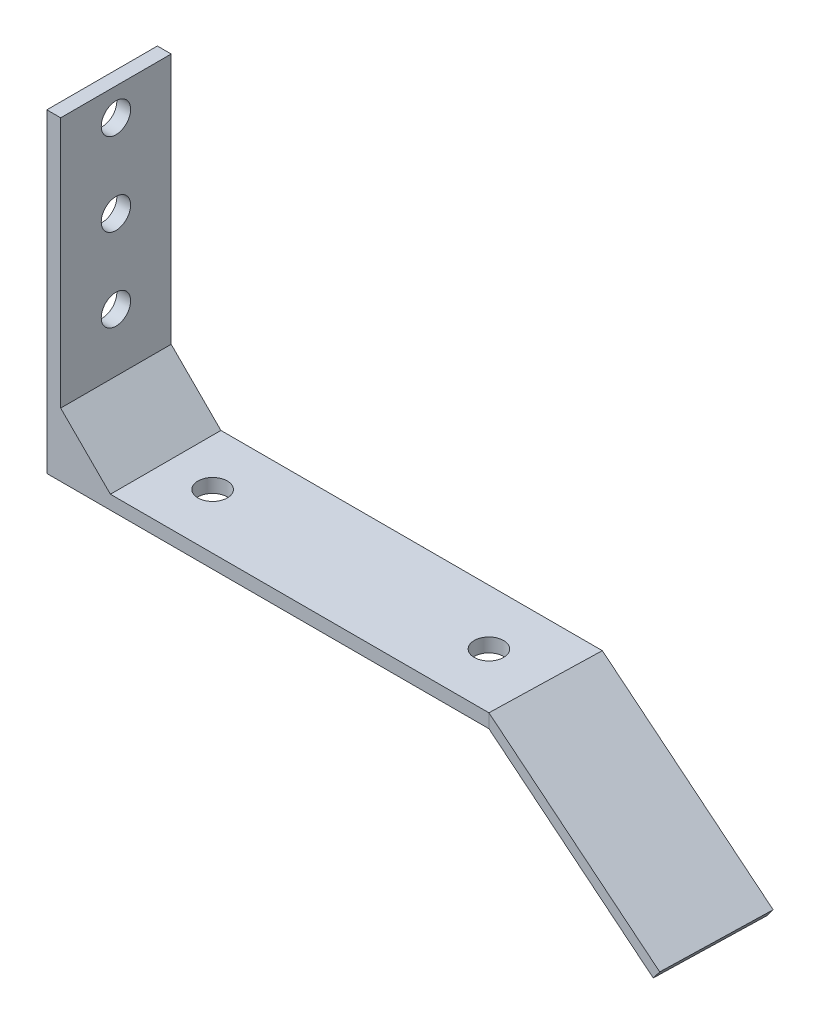
SolidWorks part; units mm, degrees
ref_plane "Front Plane" through (0, 0, 0) normal (0, 0, 1) x (1, 0, 0)
ref_plane "Top Plane" through (0, 0, 0) normal (0, 1, 0) x (1, 0, 0)
ref_plane "Right Plane" through (0, 0, 0) normal (1, 0, 0) x (0, 0, -1)
sketch "Sketch1" plane through (0, 0, 0) normal (0, 0, 1) x (1, 0, 0)
  line L1 (0, 0) -> (3.175, 0)
  line L2 (0, 0) -> (0, 72.39)
  line L3 (0, 72.39) -> (3.175, 72.39)
  line L4 (3.175, 3.175) -> (3.175, 72.39)
  line L5 (0, 0) -> (101.6, 0)
  line L6 (0, 0) -> (0, 3.175)
  line L7 (3.175, 3.175) -> (101.6, 3.175)
  line L8 (101.6, 0) -> (101.6, 3.175)
  dimension "D1" = 101.6
  dimension "D2" = 3.175
  dimension "D3" = 3.175
  dimension "D4" = 72.39
extrude "Boss-Extrude1" add sketch "Sketch1" along normal blind 25.4 contours L5 L8 L7 L4 L3 L2 L1 region at (1.2475, 1.5875, 0)
sketch "Sketch2" plane through (0, 3.175, 0) normal (0, 1, 0) x (1, 0, 0)
  line L0 (101.6, -25.4) -> (101.6, 0) construction
  line L1 (3.175, -25.4) -> (101.6, -25.4) construction
  circle A0 centre (88.9, -12.7) radius 3.3782
  circle A1 centre (25.4, -12.7) radius 3.3782
  dimension "D5" = 6.7564
  dimension "D6" = 6.7564
  dimension "D2" = 63.5
  dimension "D1" = 12.7
  dimension "D3" = 12.7
  dimension "D4" = 12.7
extrude "Cut-Extrude1" cut sketch "Sketch2" against normal blind 25.4
sketch "Sketch3" plane through (0, 0, 0) normal (-1, 0, 0) x (0, 0, 1)
  line L0 (25.4, 0) -> (0, 0) construction
  line L2 (0, 3.175) -> (0, 72.39) construction
  circle A0 centre (12.7, 27.94) radius 3.3782
  circle A1 centre (12.7, 46.99) radius 3.3782
  circle A2 centre (12.7, 66.04) radius 3.3782
  dimension "D1" = 6.7564
  dimension "D2" = 6.7564
  dimension "D3" = 6.7564
  dimension "D4" = 27.94
  dimension "D5" = 19.05
  dimension "D6" = 19.05
  dimension "D7" = 12.7
  dimension "D8" = 12.7
  dimension "D9" = 12.7
extrude "Cut-Extrude2" cut sketch "Sketch3" against normal through all
sketch "Sketch4" plane through (0, 0, 25.4) normal (0, 0, 1) x (1, 0, 0)
  line L0 (3.175, 14.605) -> (14.605, 3.175)
  line L1 (3.175, 3.175) -> (3.175, 72.39) construction
  line L2 (3.175, 3.175) -> (101.6, 3.175) construction
  line L3 (14.605, 3.175) -> (3.175, 3.175)
  line L4 (3.175, 3.175) -> (3.175, 14.605)
  dimension "D1" = 45
  dimension "D2" = 11.43
extrude "Boss-Extrude2" add sketch "Sketch4" against normal blind 25.4
sketch "Sketch5" plane through (0, 3.175, 0) normal (0, 1, 0) x (1, 0, 0)
  line L0 (101.6, -25.4) -> (102.2651, 0)
  line L1 (102.2651, 0) -> (101.6, 0)
  line L2 (101.6, 0) -> (96.08, -4.1638)
  line L3 (96.08, -4.1638) -> (98.1305, -10.2156)
  line L4 (98.1305, -10.2156) -> (94.0294, -12.2161)
  line L5 (94.0294, -12.2161) -> (96.08, -18.2679)
  line L6 (96.08, -18.2679) -> (92.6626, -19.9349)
  line L7 (92.6626, -19.9349) -> (98.1305, -22.4716)
  line L8 (98.1305, -22.4716) -> (98.84, -24.5653)
  line L9 (98.84, -24.5653) -> (101.6, -25.4)
  dimension "D1" = 88.5
extrude "Boss-Extrude3" add sketch "Sketch5" against normal up to surface (3.175 mm away) up to face at (25.4, 0, 16.0782)
ref_plane "Plane1" through (39.3186, 51.3512, 1.0296) normal (0.6079, 0.7939, 0.0159) x (0.0262, 0, -0.9997)
sketch "Sketch6" plane through (39.3186, 51.3512, 1.0296) normal (0.6079, 0.7939, 0.0159) x (0.0262, 0, -0.9997)
  line L0 (-22.7317, -79.2282) -> (-22.7317, -130.0282)
  line L2 (-22.7317, -130.0282) -> (2.677, -130.0282)
  line L3 (2.677, -79.2282) -> (2.677, -130.0282)
  line L7 (-22.7317, -79.2282) -> (2.677, -79.2282)
  dimension "D1" = 50.8
extrude "Boss-Extrude4" add sketch "Sketch6" against normal up to vertex (2.5206 mm away) up to point (102.2651, 0, 0)
sketch "Sketch7" plane through (0, 0, 0) normal (-1, 0, 0) x (0, 0, 1)
  line L0 (0, 0) -> (0, 72.39) construction
  line L1 (0, 12.8186) -> (-4.5061, 12.8186)
  line L2 (0, 12.8186) -> (0, 0)
  line L3 (0, 0) -> (-4.5061, 0)
  line L4 (-4.5061, 12.8186) -> (-4.5061, 0)
extrude "Cut-Extrude3" cut sketch "Sketch7" against normal through all
